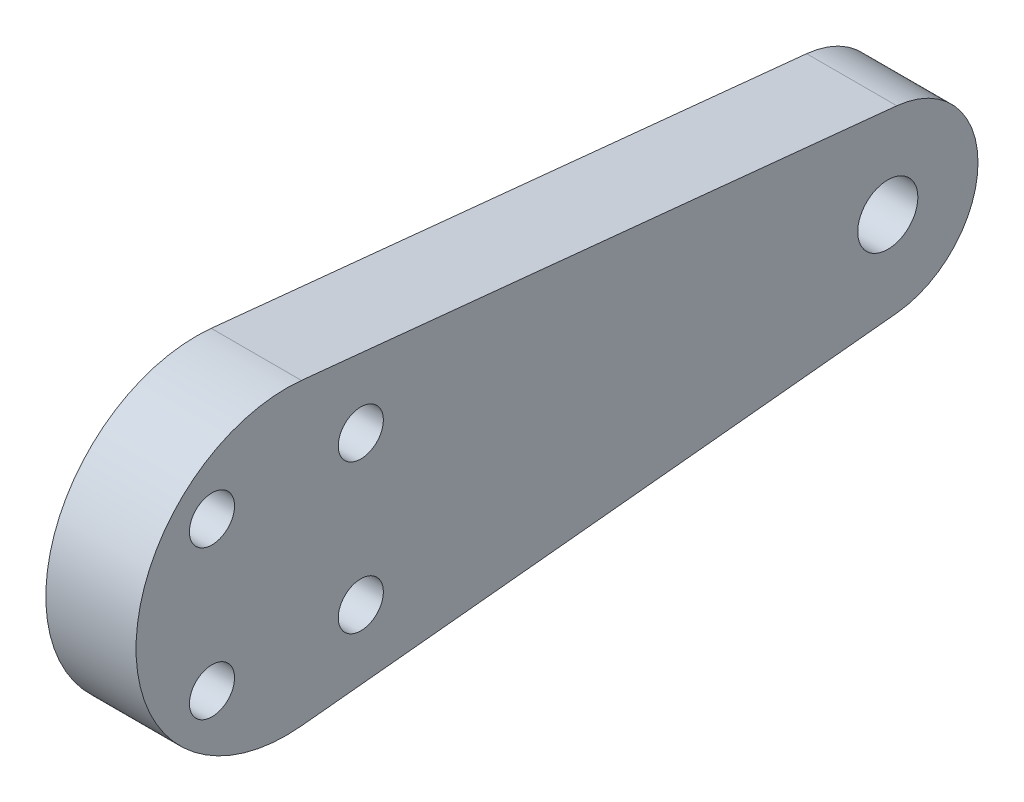
SolidWorks part; units mm, degrees
ref_plane "Front Plane" through (0, 0, 0) normal (0, 0, 1) x (1, 0, 0)
ref_plane "Top Plane" through (0, 0, 0) normal (0, 1, 0) x (1, 0, 0)
ref_plane "Right Plane" through (0, 0, 0) normal (1, 0, 0) x (0, 0, -1)
sketch "length (ref to equation file)" plane through (0, 0, 0) normal (1, 0, 0) x (0, 0, -1)
  line L0 (0, 0) -> (40, 0)
  dimension "D1" = 40
ref_axis "motor pivot" through (0, 0, 0) along (1, 0, 0)
ref_axis "pivot w/ link 2" through (0, 0, -40) along (1, 0, 0)
sketch "Sketch1" plane through (0, 0, 0) normal (1, 0, 0) x (0, 0, -1)
  line L3 (40.6, 5.9699) -> (1, 9.9499)
  line L4 (40.6, -5.9699) -> (1, -9.9499)
  circle A2 centre (0, 0) radius 10
  circle A3 centre (40, 0) radius 6
  arc A4 (7.0711, 7.0711) -> (-7.0711, -7.0711) centre (0, 0) ccw construction
  dimension "D1" = 12
extrude "Boss-Extrude1" add sketch "Sketch1" along normal mid plane 6 contours A2 | A3 L3 A2 L4 | A3
sketch "Sketch2" plane through (0, 0, 0) normal (1, 0, 0) x (0, 0, -1)
  arc A0 (-3.8891, -3.8891) -> (-6.0104, -6.0104) centre (-4.9497, -4.9497) ccw construction
  arc A1 (-6.0104, -6.0104) -> (-3.8891, -3.8891) centre (-4.9497, -4.9497) ccw construction
  arc A2 (6.0104, -3.8891) -> (3.8891, -6.0104) centre (4.9497, -4.9497) ccw construction
  arc A3 (3.8891, -6.0104) -> (6.0104, -3.8891) centre (4.9497, -4.9497) ccw construction
  arc A4 (-6.0104, 3.8891) -> (-3.8891, 6.0104) centre (-4.9497, 4.9497) ccw construction
  arc A5 (-3.8891, 6.0104) -> (-6.0104, 3.8891) centre (-4.9497, 4.9497) ccw construction
  arc A6 (6.0104, 6.0104) -> (3.8891, 3.8891) centre (4.9497, 4.9497) ccw construction
  arc A7 (3.8891, 3.8891) -> (6.0104, 6.0104) centre (4.9497, 4.9497) ccw construction
  arc A8 (-3.8891, -3.8891) -> (-6.0104, -6.0104) centre (-4.9497, -4.9497) ccw construction
  arc A9 (-6.0104, -6.0104) -> (-3.8891, -3.8891) centre (-4.9497, -4.9497) ccw construction
  arc A10 (6.0104, -3.8891) -> (3.8891, -6.0104) centre (4.9497, -4.9497) ccw construction
  arc A11 (3.8891, -6.0104) -> (6.0104, -3.8891) centre (4.9497, -4.9497) ccw construction
  arc A12 (-6.0104, 3.8891) -> (-3.8891, 6.0104) centre (-4.9497, 4.9497) ccw construction
  arc A13 (-3.8891, 6.0104) -> (-6.0104, 3.8891) centre (-4.9497, 4.9497) ccw construction
  arc A14 (6.0104, 6.0104) -> (3.8891, 3.8891) centre (4.9497, 4.9497) ccw construction
  arc A15 (3.8891, 3.8891) -> (6.0104, 6.0104) centre (4.9497, 4.9497) ccw construction
  circle A16 centre (4.9497, 4.9497) radius 1.5
  circle A17 centre (4.9497, -4.9497) radius 1.5
  circle A18 centre (-4.9497, -4.9497) radius 1.5
  circle A19 centre (-4.9497, 4.9497) radius 1.5
extrude "Cut-Extrude1" cut sketch "Sketch2" against normal through all both and the other way through all
sketch "Sketch3" plane through (3, 0, 0) normal (1, 0, 0) x (0, 0, -1)
  circle A0 centre (40, 0) radius 3
  point P0 (40, 0)
  dimension "D1" = 6
hole_wizard "Ø4.0mm Dowel Hole1" positions "Sketch3" profile "Sketch4" hole size "Ø4.0" standard "ANSI Metric" end condition through all
sketch "Sketch4" plane through (3, 0, -40) normal (0, 1, 0) x (0, 0, -1)
  line L0 (0, 0) -> (0, 6)
  line L1 (0, 6) -> (2, 6)
  line L2 (2, 6) -> (2, 0)
  line L5 (2, 0) -> (0, 0)
  line L11 (0, -6.35) -> (0, 107.95) construction
  dimension "Thru Hole Dia." = 4
  dimension "Thru Hole Depth" = 6
equation "\"link 1\" = 40mm"
equation "\"D1@length (ref to equation file)\" = \"link 1\""
equation "\"link 1 thickness\" = 6mm"
equation "\"D1@Boss-Extrude1\"=\"link 1 thickness\""
equation "\"motor center z\" = 35mm"
equation "\"motor center y\" = 20mm"
equation "\"link 2\"= 110mm"
equation "\"pivot height\"= 100mm"
equation "\"beam length\"= 400mm"
equation "\"camera height\"= 250mm"
equation "\"link height\" = 12mm"
equation "\"beam width\"= 28.5mm"
equation "\"beam side wall thickness\"= 3mm"
equation "\"D1@Sketch1\"=\"link height\""
